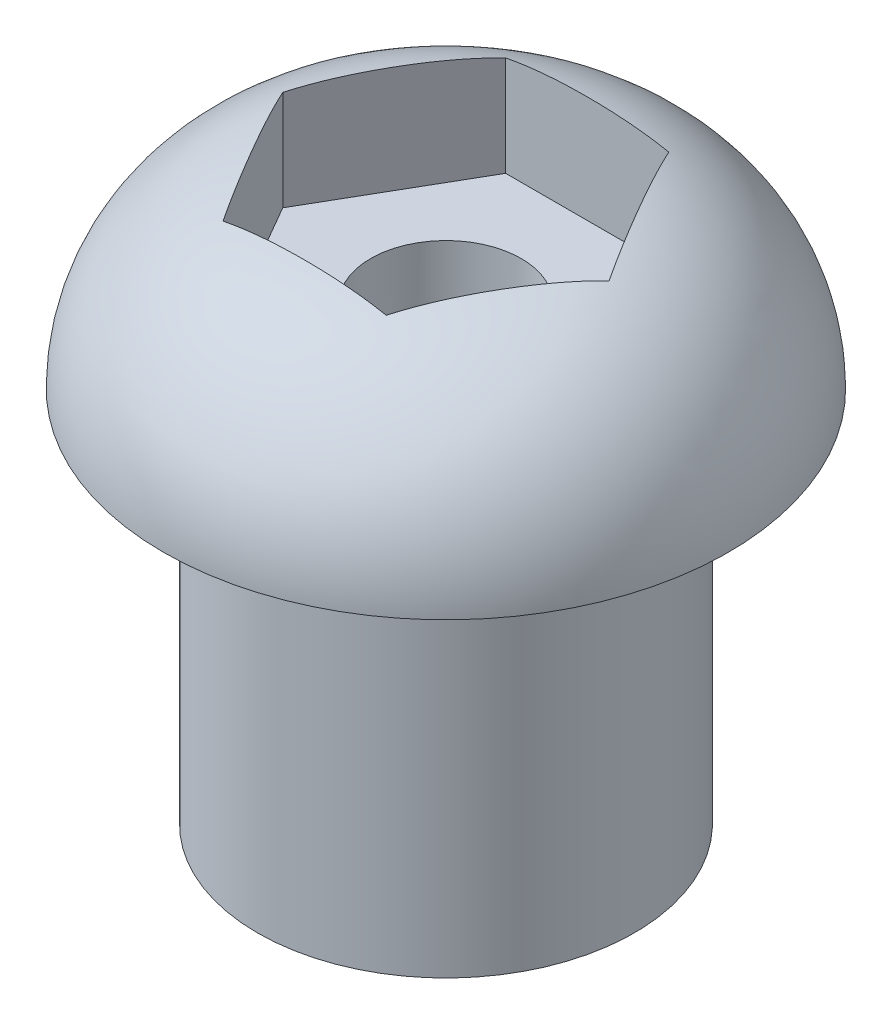
SolidWorks part; units mm, degrees
ref_plane "Front Plane" through (0, 0, 0) normal (0, 0, 1) x (1, 0, 0)
ref_plane "Top Plane" through (0, 0, 0) normal (0, 1, 0) x (1, 0, 0)
ref_plane "Right Plane" through (0, 0, 0) normal (1, 0, 0) x (0, 0, -1)
sketch "Sketch1" plane through (0, 0, 0) normal (0, 0, 1) x (1, 0, 0)
  line L0 (0, 0) -> (-3.175, 0)
  line L1 (-3.175, 0) -> (-3.175, 6.35)
  line L3 (-4.7625, 9.525) -> (0, 9.525)
  line L4 (0, 9.525) -> (0, 0) construction
  line L5 (-3.175, 6.35) -> (-4.7625, 6.35)
  line L6 (-4.7625, 6.35) -> (-4.7625, 9.525)
  line L7 (0, 0) -> (0, 9.525)
  dimension "D1" = 6.35
  dimension "D2" = 6.35
  dimension "D3" = 3.175
  dimension "D4" = 9.525
revolve "Revolve1" add sketch "Sketch1" angle 360 about L4
sketch "Sketch2" plane through (0, 9.525, 0) normal (0, 1, 0) x (1, 0, 0)
  line L1 (-1.3748, -2.3812) -> (1.3748, -2.3813)
  line L2 (1.3748, -2.3813) -> (2.7496, 0)
  line L3 (2.7496, 0) -> (1.3748, 2.3813)
  line L4 (1.3748, 2.3813) -> (-1.3748, 2.3813)
  line L5 (-1.3748, 2.3813) -> (-2.7496, 0)
  line L6 (-2.7496, 0) -> (-1.3748, -2.3812)
  circle A0 centre (0, 0) radius 2.3813 construction
  dimension "D1" = 4.7625
extrude "Cut-Extrude1" cut sketch "Sketch2" against normal blind 1.905
sketch "Sketch3" plane through (0, 7.62, 0) normal (0, 1, 0) x (1, 0, 0)
  circle A0 centre (0, 0) radius 1.27
  dimension "D1" = 2.54
extrude "Cut-Extrude2" cut sketch "Sketch3" against normal up to next
sketch "Sketch4" plane through (0, 0, 0) normal (0, -1, 0) x (1, 0, 0)
  circle A0 centre (0, 0) radius 2.3495
  dimension "D1" = 4.699
extrude "Cut-Extrude3" cut sketch "Sketch4" against normal up to surface (6.35 mm away) up to face at (0, 6.35, 3.175)
fillet "Fillet1" radius 3.175 1 edges at (0, 9.525, 4.7625)
